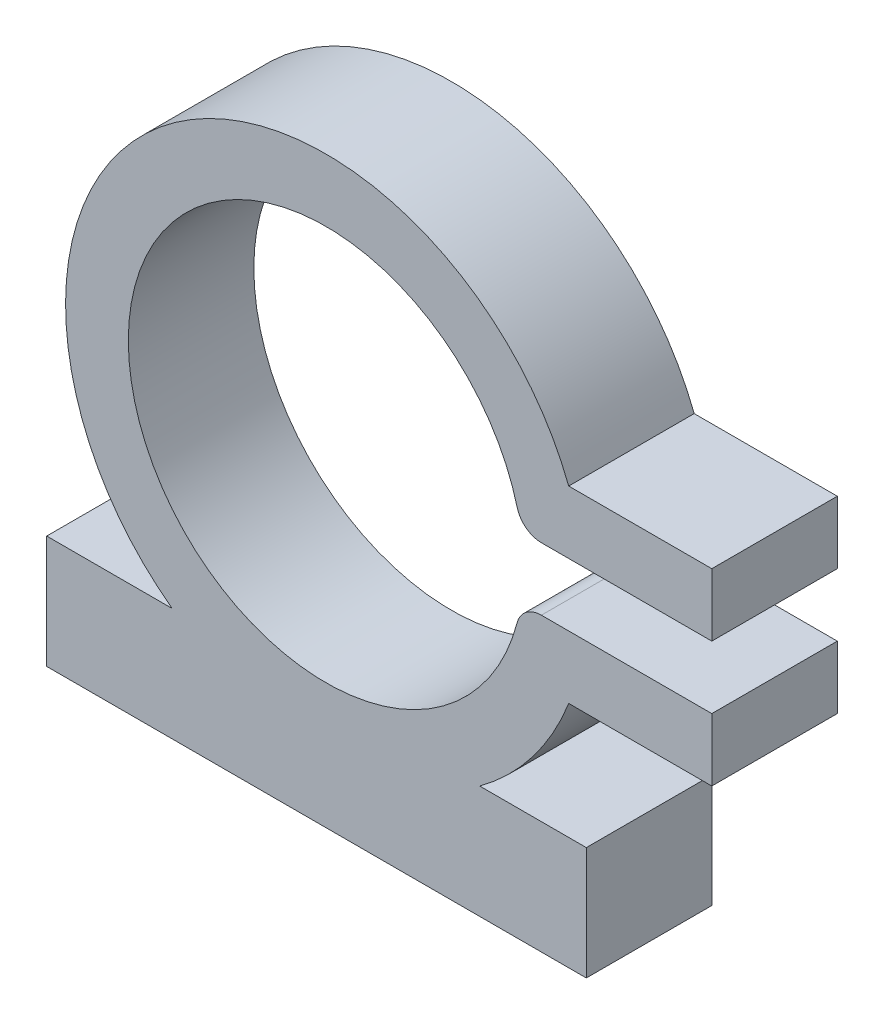
SolidWorks part; units mm, degrees
ref_plane "Front Plane" through (0, 0, 0) normal (0, 0, 1) x (1, 0, 0)
ref_plane "Top Plane" through (0, 0, 0) normal (0, 1, 0) x (1, 0, 0)
ref_plane "Right Plane" through (0, 0, 0) normal (1, 0, 0) x (0, 0, -1)
sketch "Sketch1" plane through (0, 0, 0) normal (0, 0, 1) x (1, 0, 0)
  line L0 (0, 0) -> (39.05, 0)
  line L5 (39.05, -9.525) -> (39.05, 9.525)
  line L6 (0, -9.525) -> (0, 9.525)
  line L7 (0, -3.175) -> (39.05, -3.175)
  line L8 (0, 3.175) -> (39.05, 3.175)
  line L9 (0, -3.175) -> (39.05, -3.175)
  line L10 (0, -9.525) -> (39.05, -9.525)
  line L11 (0, 9.525) -> (39.05, 9.525)
  line L12 (0, 3.175) -> (39.05, 3.175)
  line L13 (26.35, 0) -> (26.35, 3.175) construction
  line L22 (26.35, 3.175) -> (26.35, -3.175) construction
  line L24 (-28.26, -26.35) -> (26.35, -26.35)
  line L25 (-28.26, -26.35) -> (-28.26, -32.7)
  line L26 (-28.26, -32.7) -> (26.35, -32.7)
  line L27 (26.35, -26.35) -> (26.35, -32.7)
  line L28 (-28.26, -26.35) -> (26.35, -26.35)
  line L29 (-28.26, -26.35) -> (-28.26, -21.27)
  line L30 (-28.26, -21.27) -> (26.35, -21.27)
  line L31 (26.35, -26.35) -> (26.35, -21.27)
  circle A0 centre (0, 0) radius 20
  circle A1 centre (0, 0) radius 26.35
  point P0 (0, 0)
  point P3 (0, 0)
  point P22 (0, -27.305)
  dimension "D3" = 40
  dimension "D2" = 52.7
  dimension "D10" = 5.08
  dimension "D4" = 12.7
  dimension "D5" = 3.175
  dimension "D6" = 3.175
  dimension "D7" = 6.35
  dimension "D8" = 6.35
extrude "Boss-Extrude1" add sketch "Sketch1" along normal blind 12.7 contours L11 A1 L30 L10 A0 | A1 L30 L29 L24 L31 | L30 A1 | L27 L24 L25 L26 | L10 A1 L9 A0 | L12 A1 L11 A0 | A1 L8 L5 L11 | A1 L10 L5 L7 | L29 L28 L31 L30 region at (22.1713, 6.3948, 0) region at (22.1713, -6.3948, 0) region at (32.2689, 6.4119, 0) region at (32.2689, -6.4119, 0) region at (-20.6972, 0, 0) region at (-19.0508, -24.1037, 0) region at (0, -23.3198, 0) region at (-0.955, -29.525, 0)
fillet "Fillet2" radius 2.54 2 edges at (19.7464, -3.175, 6.35) (19.7464, 3.175, 6.35)
equation "\"D2@Sketch1\"=\"D3@Sketch1\"+.5"
